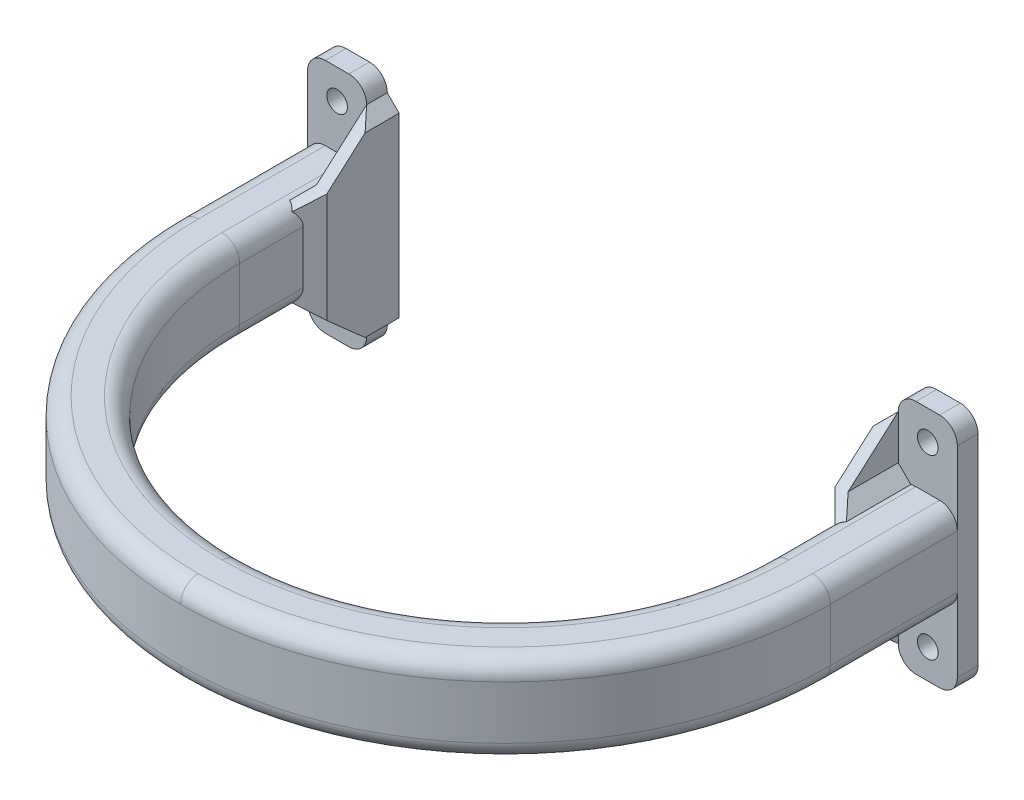
SolidWorks part; units mm, degrees
ref_plane "Front Plane" through (0, 0, 0) normal (0, 0, 1) x (1, 0, 0)
ref_plane "Top Plane" through (0, 0, 0) normal (0, 1, 0) x (1, 0, 0)
ref_plane "Right Plane" through (0, 0, 0) normal (1, 0, 0) x (0, 0, -1)
sketch "Sketch1" plane through (0, 0, 0) normal (0, 0, 1) x (1, 0, 0)
  line L0 (-50, 0) -> (0, 0) construction
  line L1 (-52, 20) -> (-48, 20)
  line L2 (-55, 17) -> (-55, -17)
  line L3 (-52, -20) -> (-48, -20)
  line L4 (-45, 17) -> (-45, -17)
  line L5 (-55, 20) -> (-45, -20) construction
  line L6 (-55, -20) -> (-45, 20) construction
  line L7 (-50, 15) -> (-50, -15) construction
  line L8 (0, -55) -> (0, 55) construction
  line L9 (50, 15) -> (50, -15) construction
  line L10 (55, -20) -> (45, 20) construction
  line L11 (55, 20) -> (45, -20) construction
  line L12 (45, 17) -> (45, -17)
  line L13 (52, -20) -> (48, -20)
  line L14 (55, 17) -> (55, -17)
  line L15 (52, 20) -> (48, 20)
  circle A0 centre (-50, 15) radius 1.75
  circle A1 centre (-50, -15) radius 1.75
  arc A2 (-55, -17) -> (-52, -20) centre (-52, -17) ccw
  arc A3 (-48, -20) -> (-45, -17) centre (-48, -17) ccw
  arc A4 (-48, 20) -> (-45, 17) centre (-48, 17) cw
  arc A5 (-52, 20) -> (-55, 17) centre (-52, 17) ccw
  arc A6 (52, 20) -> (55, 17) centre (52, 17) cw
  arc A7 (48, 20) -> (45, 17) centre (48, 17) ccw
  arc A8 (48, -20) -> (45, -17) centre (48, -17) cw
  arc A9 (55, -17) -> (52, -20) centre (52, -17) cw
  circle A10 centre (50, -15) radius 1.75
  circle A11 centre (50, 15) radius 1.75
  point P0 (-50, 0)
  point P46 (50, 0)
  dimension "D4" = 3.5
  dimension "D6" = 3
  dimension "D1" = 50
  dimension "D2" = 10
  dimension "D3" = 40
  dimension "D5" = 30
extrude "Boss-Extrude1" add sketch "Sketch1" along normal blind 3.5
sketch "Sketch3" plane through (0, 0, 0) normal (0, 1, 0) x (1, 0, 0)
  line L0 (-45, -3.5) -> (-55, -3.5)
  line L1 (-55, -3.5) -> (-55, -25)
  line L2 (-55, -25) -> (-45, -25) construction
  line L3 (-45, -25) -> (-45, -3.5)
  line L4 (0, -70) -> (0, 0) construction
  line L5 (0, -70) -> (0, -80)
  arc A0 (-45, -25) -> (0, -70) centre (0, -25) ccw
  arc A1 (-55, -25) -> (0, -80) centre (0, -25) ccw
  dimension "D1" = 70
extrude "Boss-Extrude2" add sketch "Sketch3" along normal mid plane 15
sketch "Sketch4" plane through (-45, 0, 0) normal (1, 0, 0) x (0, 0, -1)
  line L0 (-14.25, 7.5) -> (-3.5, 17)
  line L1 (-25, 7.5) -> (-3.5, 7.5) construction
  line L2 (-3.5, 17) -> (0, 17)
  line L3 (0, 17) -> (0, -17)
  line L4 (0, -17) -> (-3.5, -17)
  line L5 (-3.5, -17) -> (-14.25, -7.5)
  line L6 (-25, -7.5) -> (-3.5, -7.5) construction
  line L7 (-14.25, -7.5) -> (-14.25, 7.5)
  line L8 (-3.5, 17) -> (0, 17) construction
  line L9 (-3.5, 7.5) -> (-3.5, 17) construction
  point P14 (-3.4703, 17)
  point P17 (-3.4837, 17)
  point P18 (-3.5, 17)
extrude "Boss-Extrude3" add sketch "Sketch4" along normal blind 2
chamfer "Chamfer1" distance 2 angle 45 5 edges at (-43, -17, 1.75) (-43, 17, 1.75) (-43, 0, 14.25) (-45, -7.5, 8.875) (-45, 7.5, 8.875)
fillet "Fillet1" radius 3 8 edges at (-45, -7.5, 19.625) (-45, 7.5, 19.625) (-31.8198, -7.5, 56.8198) (-31.8198, 7.5, 56.8198) (-55, -7.5, 14.25) (-55, 7.5, 14.25) (-38.8909, -7.5, 63.8909) (-38.8909, 7.5, 63.8909)
mirror "Mirror3" about plane through (0, 0, 0) normal (1, 0, 0) of "Fillet1", "Chamfer1", "Boss-Extrude3", "Boss-Extrude2"
